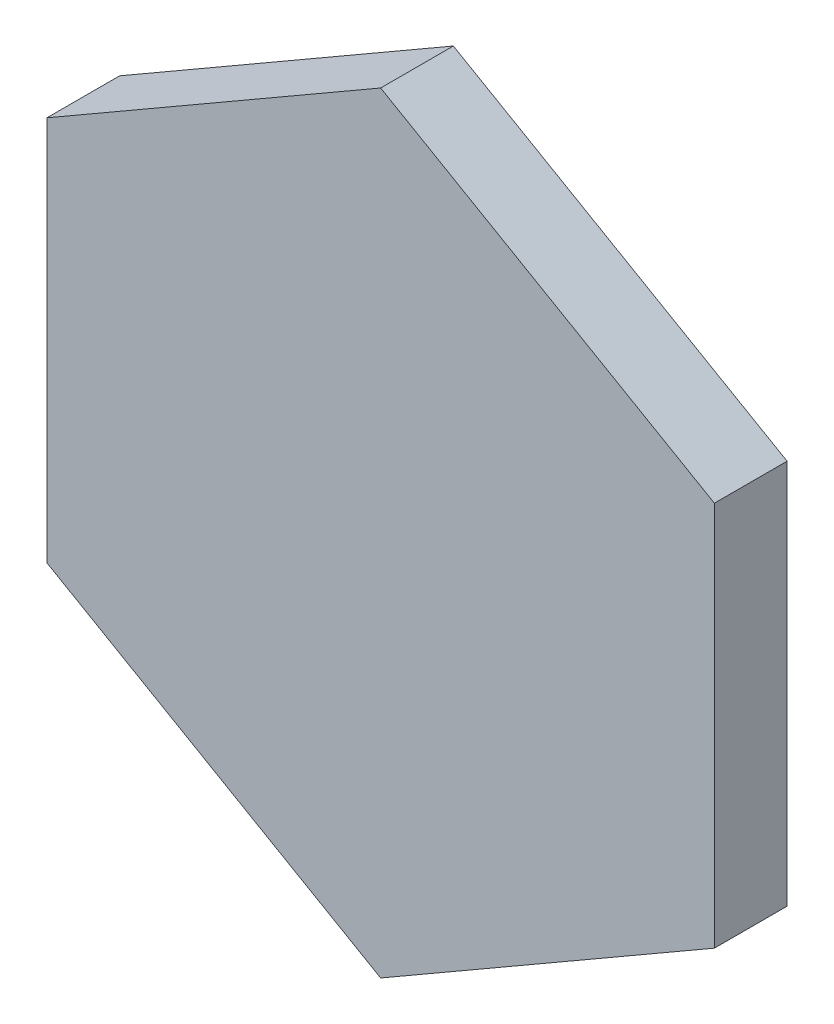
SolidWorks part; units mm, degrees
ref_plane "Front Plane" through (0, 0, 0) normal (0, 0, 1) x (1, 0, 0)
ref_plane "Top Plane" through (0, 0, 0) normal (0, 1, 0) x (1, 0, 0)
ref_plane "Right Plane" through (0, 0, 0) normal (1, 0, 0) x (0, 0, -1)
sketch "Sketch1" plane through (0, 0, 0) normal (0, 0, 1) x (1, 0, 0)
  line L0 (0, -26.6667) -> (0, 13.3333) construction
  line L1 (4.4264, -19) -> (23.094, 13.3333)
  line L2 (23.094, 13.3333) -> (-23.094, 13.3333) construction
  line L3 (-23.094, 13.3333) -> (-4.4264, -19)
  line L4 (-15.396, 13.3333) -> (-8.1791, 0.8333) construction
  line L5 (0, -13.3333) -> (7.2169, -0.8333)
  line L6 (-13.0866, 13.3333) -> (0, -9.3333)
  line L7 (3.849, -20) -> (-3.849, -20) construction
  line L8 (-3.849, -20) -> (0, -13.3333) construction
  line L9 (3.849, -20) -> (0, -13.3333) construction
  line L10 (15.396, 13.3333) -> (19.245, 6.6667)
  line L11 (-15.396, 13.3333) -> (-19.245, 6.6667)
  line L12 (0, -11.3333) -> (14.2413, 13.3333)
  line L13 (0, -11.3333) -> (-14.2413, 13.3333)
  line L14 (-14.2413, 13.3333) -> (-18.6677, 5.6667)
  line L15 (-7.0244, 0.8333) -> (-12.0281, 0.8333)
  line L16 (-12.0281, 0.8333) -> (-11.0659, -0.8333)
  line L17 (-19.245, 6.6667) -> (-18.379, 6.1667) construction
  line L18 (14.2413, 13.3333) -> (18.6677, 5.6667)
  line L19 (-11.0659, -0.8333) -> (-6.0622, -0.8333)
  line L20 (-4.4264, -19) -> (4.4264, -19)
  line L21 (7.0244, 0.8333) -> (12.0281, 0.8333)
  line L22 (12.0281, 0.8333) -> (11.0659, -0.8333)
  line L23 (-3.849, -20) -> (-3.849, -19) construction
  line L24 (0, -9.3333) -> (13.0866, 13.3333)
  line L25 (19.245, 6.6667) -> (18.379, 6.1667) construction
  line L26 (11.0659, -0.8333) -> (6.0622, -0.8333)
  line L27 (12.9904, -4.1667) -> (10.1036, -2.5) construction
  line L28 (10.1036, -2.5) -> (7.2169, -0.8333) construction
  line L30 (-3.849, -20) -> (0, -26.6667) construction
  line L31 (0, -26.6667) -> (3.849, -20) construction
  line L32 (-3.849, -20) -> (-4.4264, -19) construction
  line L33 (3.849, -20) -> (4.4264, -19) construction
  line L34 (-7.2169, -0.8333) -> (0, -13.3333)
  line L35 (8.1791, 0.8333) -> (15.396, 13.3333) construction
  line L36 (7.2169, -0.8333) -> (8.1791, 0.8333) construction
  line L37 (-8.1791, 0.8333) -> (-7.2169, -0.8333) construction
  line L38 (13.0866, 13.3333) -> (13.9526, 12.8333) construction
  line L39 (27.5327, 15.896) -> (0, 31.792)
  line L40 (0, 31.792) -> (-27.5327, 15.896)
  line L41 (-27.5327, 15.896) -> (-27.5327, -15.896)
  line L42 (-27.5327, -15.896) -> (0, -31.792)
  line L43 (0, -31.792) -> (27.5327, -15.896)
  line L44 (27.5327, -15.896) -> (27.5327, 15.896)
  line L45 (-23.094, 13.3333) -> (-15.396, 13.3333)
  line L46 (23.094, 13.3333) -> (15.396, 13.3333)
  line L47 (-13.0866, 13.3333) -> (13.0866, 13.3333)
  line L48 (-23.094, 13.3333) -> (-26.6667, 15.396) construction
  line L49 (0, 30.792) -> (-26.6667, 15.396)
  line L50 (-26.6667, 15.396) -> (-26.6667, -15.396)
  line L51 (-26.6667, -15.396) -> (0, -30.792)
  line L52 (0, -30.792) -> (26.6667, -15.396)
  line L53 (26.6667, -15.396) -> (26.6667, 15.396)
  line L54 (26.6667, 15.396) -> (0, 30.792)
  line L55 (-26.6667, 15.396) -> (-27.5327, 15.896) construction
  line L58 (10.1036, -2.5) -> (11.0659, -0.8333) construction
  circle A0 centre (0, 0) radius 13.3333 construction
  circle A1 centre (0, 0) radius 27.5327 construction
  circle A2 centre (0, 0) radius 26.6667 construction
  point P31 (-14.8187, 12.3333)
  point P36 (-11.547, 0)
  point P39 (-7.2245, -0.8333)
  dimension "D1" = 40
  dimension "D2" = 1
extrude "Boss-Extrude1" add sketch "Sketch1" along normal blind 6 contours L41 L42 L43 L44 L39 L40
extrude "Boss-Extrude2" add sketch "Sketch1<3>" against normal blind 0.5 contours L53 L54 L49 L50 L51 L52 L6 L47 L24 L46 L1 L20 L3 L45 L11 L14 L13 L12 L18 L10 | L26 L22 L21 L12 | L16 L19 L13 L15 region at (9.0452, 0, 0) region at (-9.0452, 0, 0) region at (12.926, 22.3885, 0)
sketch "Sketch1<3>" plane through (0, 0, 0) normal (0, 0, 1) x (1, 0, 0) same geometry as "Sketch1"
